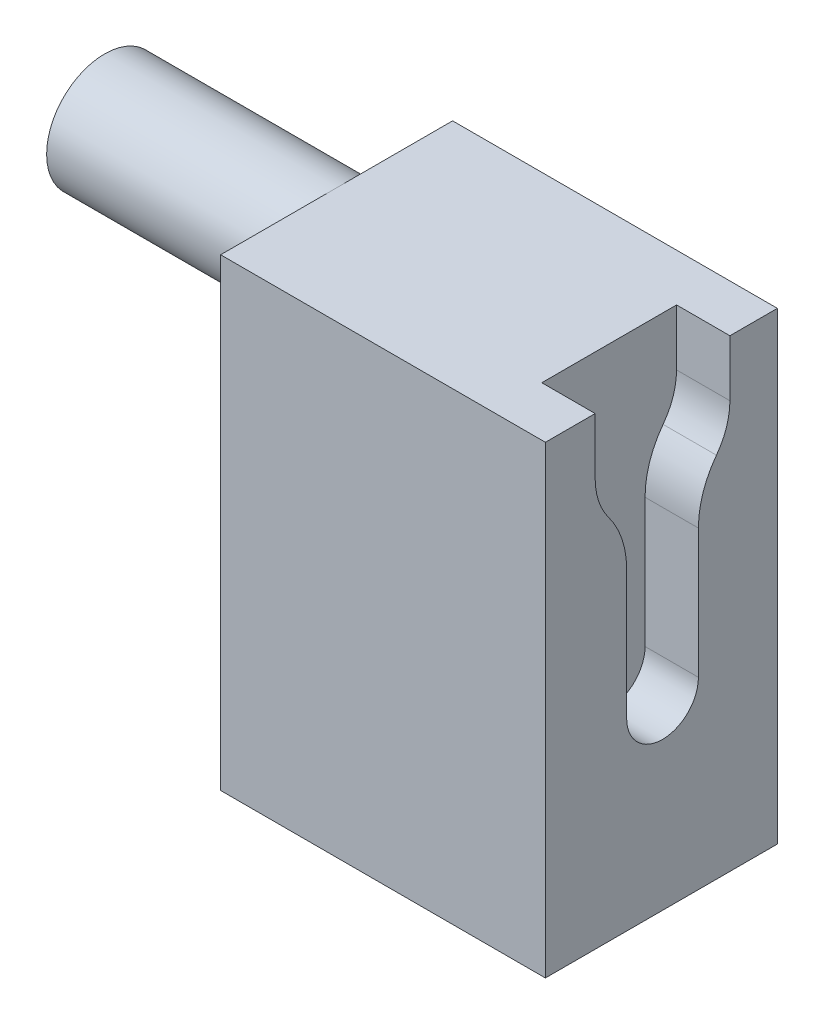
SolidWorks part; units mm, degrees
ref_plane "Front Plane" through (0, 0, 0) normal (0, 0, 1) x (1, 0, 0)
ref_plane "Top Plane" through (0, 0, 0) normal (0, 1, 0) x (1, 0, 0)
ref_plane "Right Plane" through (0, 0, 0) normal (1, 0, 0) x (0, 0, -1)
sketch "Sketch1" plane through (0, 0, 0) normal (0, 1, 0) x (1, 0, 0)
  line L1 (-17.78, -12.7) -> (17.78, -12.7)
  line L2 (-17.78, -12.7) -> (-17.78, 12.7)
  line L3 (-17.78, 12.7) -> (17.78, 12.7)
  line L4 (17.78, -12.7) -> (17.78, 12.7)
  line L5 (-17.78, -12.7) -> (17.78, 12.7) construction
  line L6 (-17.78, 12.7) -> (17.78, -12.7) construction
  point P0 (0, 0)
  dimension "D1" = 25.4
  dimension "D2" = 35.56
extrude "Boss-Extrude1" add sketch "Sketch1" along normal mid plane 50.8
sketch "Sketch2" plane through (-17.78, 0, 0) normal (-1, 0, 0) x (0, 0, 1)
  line L0 (-12.7, 25.4) -> (12.7, 25.4) construction
  circle A0 centre (0, 19.05) radius 6.35
  point P4 (0, 0)
  dimension "D1" = 12.7
extrude "Boss-Extrude2" add sketch "Sketch2" along normal mid plane 50.8
sketch "Sketch4" plane through (17.78, 0, 0) normal (1, 0, 0) x (0, 0, -1)
  line L0 (-3.6729, 8.8872) -> (-3.6729, -5.2628) construction
  line L1 (3.9271, 8.8872) -> (3.9271, -5.2628) construction
  line L2 (-3.6729, 8.8872) -> (-3.6729, -5.2628) construction
  line L3 (3.9271, 8.8872) -> (3.9271, -5.2628) construction
  line L4 (-3.7999, 8.8872) -> (-3.7999, -5.2628)
  line L5 (4.0541, 8.8872) -> (4.0541, -5.2628)
  line L6 (7.5041, 19.2372) -> (7.5041, 26.6142)
  line L7 (-7.2499, 19.2372) -> (-7.2499, 26.6142)
  line L8 (7.5041, 26.6142) -> (0.1271, 26.6142)
  line L9 (0.1271, 26.6142) -> (-7.2499, 26.6142)
  arc A0 (-3.6729, 8.8872) -> (-5.6729, 14.8872) centre (-13.6729, 8.8872) ccw construction
  arc A1 (-3.6729, -5.2628) -> (0.1271, -9.0628) centre (0.1271, -5.2628) ccw construction
  arc A3 (6.0287, 14.811) -> (-5.7745, 14.811) centre (0.1271, 19.2372) ccw
  arc A8 (6.8146, 16.4372) -> (6.1271, 23.3069) centre (0.1271, 19.2372) ccw construction
  arc A9 (-3.7999, 8.8872) -> (-5.7745, 14.811) centre (-13.6729, 8.8872) ccw
  arc A10 (5.9271, 14.8872) -> (4.0992, 10.734) centre (13.9271, 8.8872) ccw construction
  arc A12 (-3.6729, 8.8872) -> (-5.6729, 14.8872) centre (-13.6729, 8.8872) ccw construction
  arc A13 (-3.6729, -5.2628) -> (3.9271, -5.2628) centre (0.1271, -5.2628) ccw construction
  arc A14 (-3.7999, -5.2628) -> (4.0541, -5.2628) centre (0.1271, -5.2628) ccw
  arc A15 (6.0287, 14.811) -> (4.0541, 8.8872) centre (13.9271, 8.8872) ccw
  arc A20 (5.9271, 14.8872) -> (-5.6729, 14.8872) centre (0.1271, 19.2372) ccw construction
  arc A22 (5.9271, 14.8872) -> (3.9271, 8.8872) centre (13.9271, 8.8872) ccw construction
  point P5 (0.1271, 26.6142)
  line M5 (12.7, 25.4) -> (-12.7, 25.4)
  dimension "D1" = 0.127
extrude "Cut-Extrude1" cut sketch "Sketch4" against normal blind 5.842 contours A15 A3 A9 L4 A14 L5 M5 | A3 L6 L8 M5 | A3 L6 M5 | A3 L7 M5 | A3 L9 L7 M5 | A3 M5 region at (17.78, 10.5355, -0.1271) region at (17.78, 23.9372, 6.3084) region at (17.78, 26.0772, 4.8398) region at (17.78, 25.8893, -0.1271) region at (17.78, 26.0772, -5.0941) region at (17.78, 23.9372, -6.5627)
